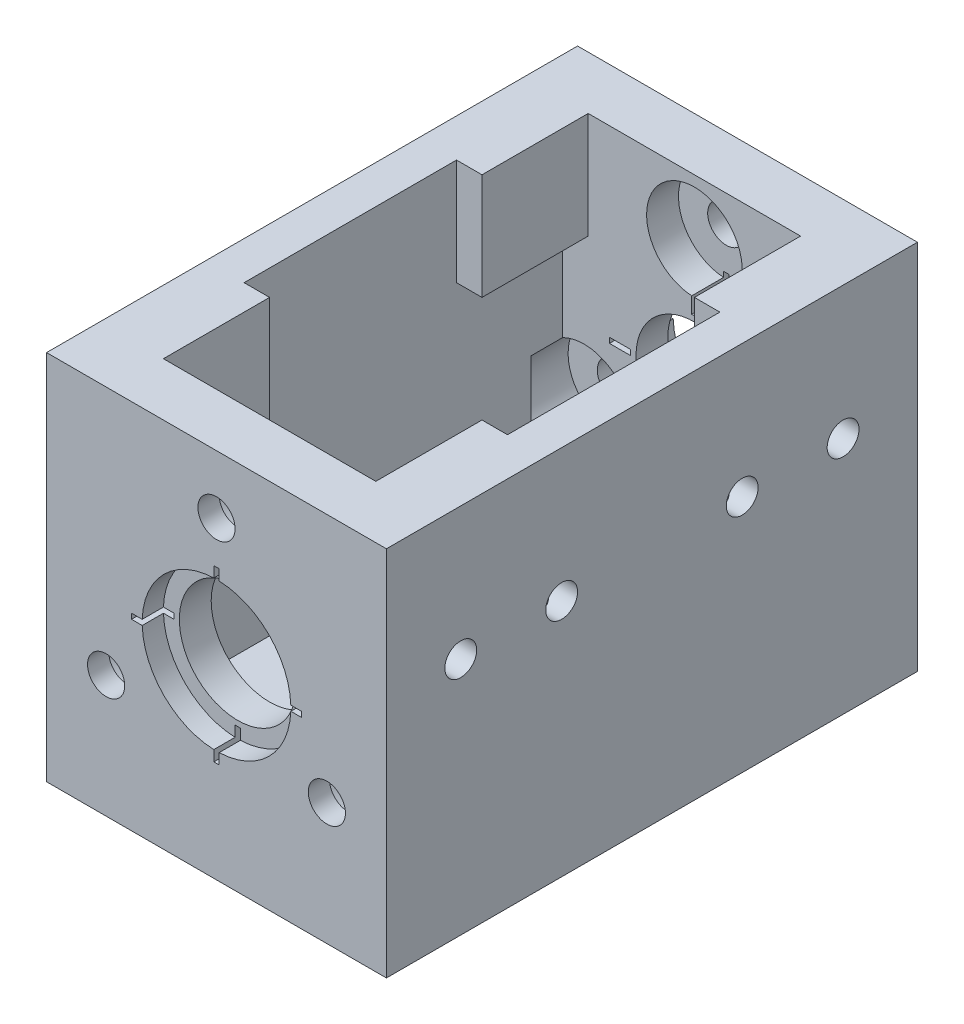
SolidWorks part; units mm, degrees
ref_plane "Front Plane" through (0, 0, 0) normal (0, 0, 1) x (1, 0, 0)
ref_plane "Top Plane" through (0, 0, 0) normal (0, 1, 0) x (1, 0, 0)
ref_plane "Right Plane" through (0, 0, 0) normal (1, 0, 0) x (0, 0, -1)
sketch "Sketch1" plane through (0, 0, 0) normal (0, 0, 1) x (1, 0, 0)
  line L1 (16, -17.5) -> (-16, -17.5)
  line L2 (16, -17.5) -> (16, 17.5)
  line L3 (16, 17.5) -> (-16, 17.5)
  line L4 (-16, -17.5) -> (-16, 17.5)
  line L5 (16, -17.5) -> (-16, 17.5) construction
  line L6 (16, 17.5) -> (-16, -17.5) construction
  point P0 (0, 0)
  dimension "D1" = 35
  dimension "D2" = 32
extrude "Boss-Extrude1" add sketch "Sketch1" along normal mid plane 50
sketch "Sketch2" plane through (0, 0, 0) normal (0, 0, 1) x (1, 0, 0)
  line L5 (-12.4, -12.5) -> (12.4, -12.5)
  line L6 (-12.4, -12.5) -> (-12.4, 12.5)
  line L7 (-12.4, 12.5) -> (12.4, 12.5)
  line L8 (12.4, -12.5) -> (12.4, 12.5)
  line L9 (-12.4, -12.5) -> (12.4, 12.5) construction
  line L10 (-12.4, 12.5) -> (12.4, -12.5) construction
  point P0 (0, 0)
  dimension "D1" = 24.8
  dimension "D2" = 25
extrude "Cut-Extrude1" cut sketch "Sketch2" against normal mid plane 40
ref_plane "Plane2" through (0, 0, 25) normal (0, 0, 1) x (1, 0, 0)
sketch "Sketch6" plane through (0, 0, 25) normal (0, 0, 1) x (1, 0, 0)
  circle A0 centre (0, 0) radius 5.5
  dimension "D1" = 11
extrude "Cut-Extrude5" cut sketch "Sketch6" against normal blind 80
ref_plane "Plane3" through (0, 17.5, 0) normal (0, 1, 0) x (1, 0, 0)
sketch "Sketch9" plane through (0, 17.5, 0) normal (0, 1, 0) x (1, 0, 0)
  line L1 (10, -20) -> (-10, -20)
  line L2 (10, -20) -> (10, 20)
  line L3 (10, 20) -> (-10, 20)
  line L4 (-10, -20) -> (-10, 20)
  line L5 (10, -20) -> (-10, 20) construction
  line L6 (10, 20) -> (-10, -20) construction
  point P0 (0, 0)
  dimension "D1" = 20
  dimension "D2" = 40
extrude "Cut-Extrude7" cut sketch "Sketch9" against normal blind 30
sketch "Sketch12" plane through (0, 0, 25) normal (0, 0, 1) x (1, 0, 0)
  circle A0 centre (0, 0) radius 7
  dimension "D1" = 14
extrude "Cut-Extrude9" cut sketch "Sketch12" against normal blind 2
sketch "Sketch13" plane through (0, 0, 25) normal (0, 0, 1) x (1, 0, 0)
  line L1 (6, 0.25) -> (8, 0.25)
  line L2 (6, 0.25) -> (6, -0.25)
  line L3 (6, -0.25) -> (8, -0.25)
  line L4 (8, 0.25) -> (8, -0.25)
  line L5 (6, 0.25) -> (8, -0.25) construction
  line L6 (6, -0.25) -> (8, 0.25) construction
  circle A0 centre (0, 0) radius 7 construction
  circle A1 centre (0, 0) radius 7 construction
  point P0 (7, 0)
  dimension "D1" = 2
  dimension "D2" = 0.5
extrude "Cut-Extrude10" cut sketch "Sketch13" against normal blind 62
pattern_circular "CirPattern2" count 4 over 360 about axis through (0, 0, 23) along (0, 0, -1) of "Cut-Extrude10"
ref_plane "Plane4" through (16, 0, 0) normal (1, 0, 0) x (0, 0, -1)
sketch "Sketch17" plane through (0, 0, 25) normal (0, 0, 1) x (1, 0, 0)
  line L0 (0, 17.2731) -> (0, -16.1686) construction
  line L1 (-17.0584, 0) -> (19.1446, 0) construction
  circle A1 centre (0, 12) radius 1.75
  dimension "D1" = 3.5
  dimension "D2" = 12
extrude "Cut-Extrude14" cut sketch "Sketch17" against normal blind 60
pattern_circular "CirPattern3" count 3 over 360 about axis through (0, 0, 23) along (0, 0, -1) of "Cut-Extrude14"
ref_plane "Plane6" through (0, 0, -20) normal (0, 0, 1) x (1, 0, 0)
sketch "Sketch19" plane through (0, 0, -20) normal (0, 0, 1) x (1, 0, 0)
  circle A0 centre (-10.3923, -6) radius 4.5
  dimension "D1" = 9
extrude "Cut-Extrude15" cut sketch "Sketch19" along normal mid plane 6
mirror "Mirror5" about plane through (0, 0, 0) normal (1, 0, 0) of "Cut-Extrude15"
mirror "Mirror6" about plane through (0, 0, 0) normal (0, 0, 1) of "Mirror5", "Cut-Extrude15"
sketch "Sketch22" plane through (0, 0, -20) normal (0, 0, 1) x (1, 0, 0)
  line L10 (-12.5, 12.5) -> (-10, 12.5)
  line L11 (-12.5, 12.5) -> (-12.5, 7.5)
  line L12 (-12.5, 7.5) -> (-10, 7.5)
  line L13 (-10, 12.5) -> (-10, 7.5)
  line L14 (-12.5, 12.5) -> (-10, 7.5) construction
  line L15 (-12.5, 7.5) -> (-10, 12.5) construction
  point P0 (-11.25, 10)
  dimension "D1" = 2.5
  dimension "D2" = 11.25
  dimension "D3" = 10
  dimension "D4" = 5
extrude "Boss-Extrude2" add sketch "Sketch22" along normal blind 45
mirror "Mirror8" about plane through (0, 0, 0) normal (1, 0, 0) of "Boss-Extrude2"
sketch "Sketch7" plane through (0, 17.5, 0) normal (0, 1, 0) x (1, 0, 0)
  line L1 (12.4, -10) -> (-12.4, -10)
  line L2 (12.4, -10) -> (12.4, 10)
  line L3 (12.4, 10) -> (-12.4, 10)
  line L4 (-12.4, -10) -> (-12.4, 10)
  line L5 (12.4, -10) -> (-12.4, 10) construction
  line L6 (12.4, 10) -> (-12.4, -10) construction
  point P0 (0, 0)
  dimension "D1" = 20
  dimension "D2" = 24.8
extrude "Cut-Extrude6" cut sketch "Sketch7" against normal blind 30
ref_plane "Plane7" through (0, -17.5, 0) normal (0, -1, 0) x (-1, 0, 0)
sketch "Sketch24" plane through (16, 0, 0) normal (1, 0, 0) x (0, 0, -1)
  circle A0 centre (-18, 5) radius 1.5
  dimension "D1" = 3
  dimension "D2" = 5
  dimension "D3" = 18
extrude "Cut-Extrude18" cut sketch "Sketch24" against normal blind 10
mirror "Mirror9" about plane through (0, 0, 0) normal (0, 0, 1) of "Cut-Extrude18"
sketch "Sketch25" plane through (0, -17.5, 0) normal (0, -1, 0) x (-1, 0, 0)
  line L6 (12.5, -11) -> (-12.5, -11)
  line L7 (12.5, -11) -> (12.5, 11)
  line L8 (12.5, 11) -> (-12.5, 11)
  line L9 (-12.5, -11) -> (-12.5, 11)
  line L10 (12.5, -11) -> (-12.5, 11) construction
  line L11 (12.5, 11) -> (-12.5, -11) construction
  point P0 (0, 0)
  dimension "D1" = 25
  dimension "D2" = 22
extrude "Cut-Extrude19" cut sketch "Sketch25" against normal blind 3
sketch "Sketch26" plane through (0, 0, -20) normal (0, 0, 1) x (1, 0, 0)
  circle A0 centre (0, 12) radius 4.5
  dimension "D1" = 9
extrude "Cut-Extrude20" cut sketch "Sketch26" against normal blind 3
mirror "Mirror10" about plane through (0, 0, 0) normal (0, 0, 1) of "Cut-Extrude20"
sketch "Sketch27" plane through (0, -17.5, 0) normal (0, -1, 0) x (-1, 0, 0)
  line L6 (0, 18.1529) -> (0, -23.3878) construction
  line L8 (-15, 5) -> (15, 5)
  line L9 (-15, 5) -> (-15, 11)
  line L10 (-15, 11) -> (15, 11)
  line L11 (15, 5) -> (15, 11)
  line L12 (-15, 5) -> (15, 11) construction
  line L13 (-15, 11) -> (15, 5) construction
  line L14 (15, -11) -> (-15, -11)
  line L15 (15, -11) -> (15, -5)
  line L16 (15, -5) -> (-15, -5)
  line L17 (-15, -11) -> (-15, -5)
  line L18 (15, -11) -> (-15, -5) construction
  line L19 (15, -5) -> (-15, -11) construction
  point P2 (0, 8)
  point P7 (0, -8)
  dimension "D1" = 8
  dimension "D2" = 6
  dimension "D3" = 30
  dimension "D4" = 6
  dimension "D5" = 8
  dimension "D6" = 30
extrude "Cut-Extrude21" [suppressed] cut sketch "Sketch27" against normal blind 4
sketch "Sketch28" plane through (0, -17.5, 0) normal (0, -1, 0) x (-1, 0, 0)
  circle A0 centre (-13, 8.5) radius 1.25
  circle A1 centre (-13, -8.5) radius 1.25
  dimension "D1" = 2.5
  dimension "D2" = 2.5
  dimension "D3" = 13
  dimension "D4" = 13
  dimension "D5" = 8.5
  dimension "D6" = 8.5
extrude "Cut-Extrude22" cut sketch "Sketch28" against normal blind 22
fillet "Fillet1" radius 1 2 edges at (11.75, -14.5, 8.5) (11.75, -14.5, -8.5)
sketch "Sketch29" plane through (16, 0, 0) normal (1, 0, 0) x (0, 0, -1)
  line L0 (-18, 5) -> (18, 5) construction
  circle A0 centre (-8.5, 5) radius 1.5
  circle A1 centre (8.5, 5) radius 1.5
  dimension "D1" = 3
  dimension "D2" = 3
  dimension "D3" = 8.5
  dimension "D4" = 8.5
extrude "Cut-Extrude23" cut sketch "Sketch29" against normal blind 10
chamfer "Chamfer1" [suppressed] distance 2 angle 45
mirror "Mirror11" about plane through (0, 0, 0) normal (0, 0, 1) of "Cut-Extrude9"
